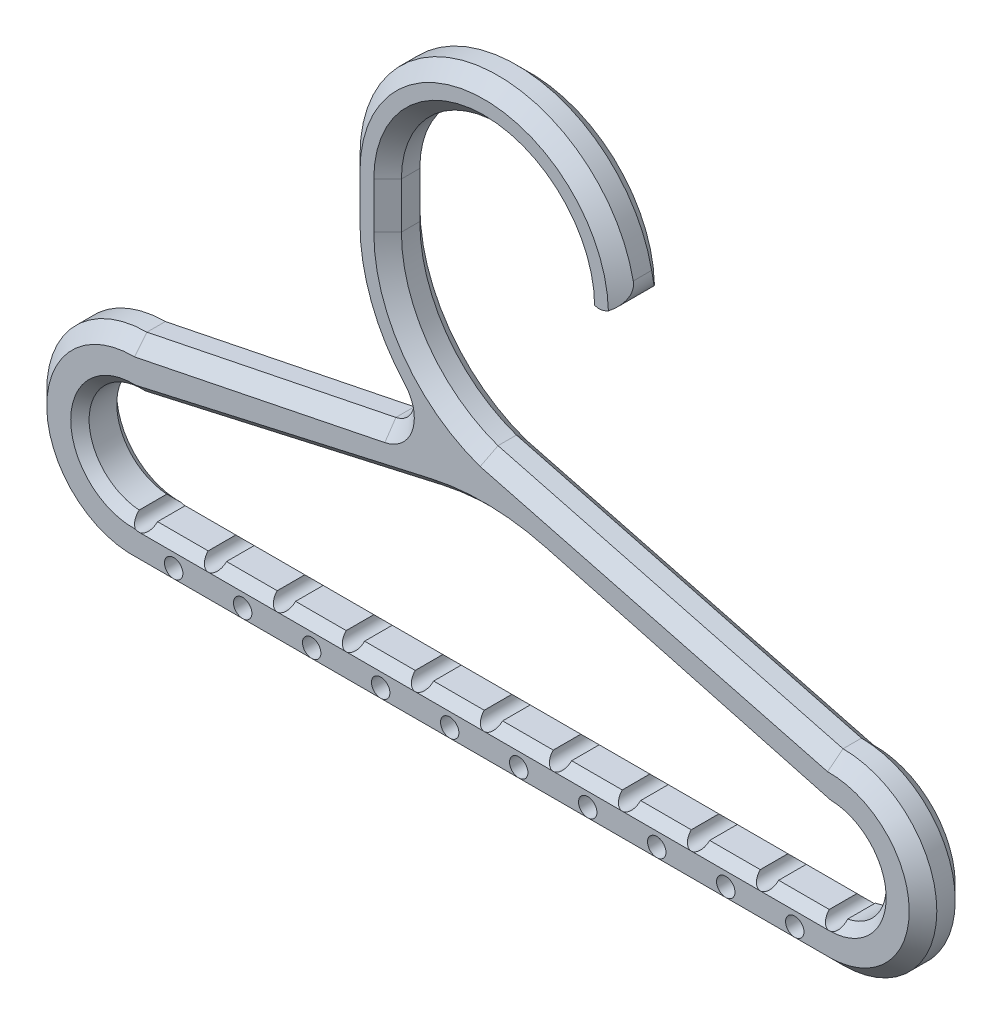
SolidWorks part; units mm, degrees
ref_plane "Front Plane" through (0, 0, 0) normal (0, 0, 1) x (1, 0, 0)
ref_plane "Top Plane" through (0, 0, 0) normal (0, 1, 0) x (1, 0, 0)
ref_plane "Right Plane" through (0, 0, 0) normal (1, 0, 0) x (0, 0, -1)
sketch "Sketch1" plane through (0, 0, 0) normal (0, 0, 1) x (1, 0, 0)
  line L0 (8.5, -40) -> (14, -40)
  line L1 (-36.5, -40) -> (-31, -40)
  line L2 (10.5, 5) -> (15, 5)
  line L3 (-36.5, -40) -> (-31, -40)
  line L5 (-37.5, -45) -> (37.5, -45)
  line L7 (-29, -40) -> (-23.5, -40)
  line L17 (6.4815, -21.2975) -> (37.5, -29.624)
  line L18 (-15, 0) -> (-15, 5)
  line L20 (0, -14.8492) -> (37.5, -24.624)
  line L21 (-11.0987, -17.7384) -> (-38.154, -23.2413)
  line L22 (-5.5107, -21.0576) -> (-37.8126, -28.3574)
  line L23 (-29, -40) -> (-23.5, -40)
  line L24 (-21.5, -40) -> (-16, -40)
  line L25 (-21.5, -40) -> (-16, -40)
  line L26 (-14, -40) -> (-8.5, -40)
  line L27 (-14, -40) -> (-8.5, -40)
  line L28 (-6.5, -40) -> (-1, -40)
  line L29 (-6.5, -40) -> (-1, -40)
  line L30 (1, -40) -> (6.5, -40)
  line L31 (1, -40) -> (6.5, -40)
  line L32 (8.5, -40) -> (14, -40)
  line L33 (16, -40) -> (21.5, -40)
  line L34 (16, -40) -> (21.5, -40)
  line L35 (23.5, -40) -> (29, -40)
  line L36 (23.5, -40) -> (29, -40)
  line L37 (31, -40) -> (36.5, -40)
  line L38 (31, -40) -> (36.5, -40)
  line L39 (-10.5, 0) -> (-10.5, 5)
  line L41 (-15, 5) -> (-15, 0)
  arc A2 (-10.5, 0) -> (0, -14.8492) centre (5.25, 0) ccw
  arc A3 (-15, 0) -> (-9.7457, -13.6085) centre (5.25, 0) ccw
  arc A7 (-9.7457, -13.6085) -> (-11.0987, -17.7384) centre (-11.597, -15.2886) cw
  arc A8 (38.4953, -39.9036) -> (37.5, -29.624) centre (37.5, -34.812) ccw
  arc A9 (37.5, -45) -> (37.5, -24.624) centre (37.5, -34.812) ccw
  arc A10 (-37.5, -45) -> (-38.154, -23.2413) centre (-38.154, -34.1305) cw
  arc A11 (-38.4953, -39.9036) -> (-37.8126, -28.3574) centre (-38.154, -34.1305) cw
  arc A12 (6.4815, -21.2975) -> (-5.5107, -21.0576) centre (0, -45.4427) ccw
  arc A13 (36.5, -40) -> (38.4953, -39.9036) centre (37.5, -40) ccw
  arc A14 (29, -40) -> (31, -40) centre (30, -40) ccw
  arc A15 (21.5, -40) -> (23.5, -40) centre (22.5, -40) ccw
  arc A16 (14, -40) -> (16, -40) centre (15, -40) ccw
  arc A17 (6.5, -40) -> (8.5, -40) centre (7.5, -40) ccw
  arc A18 (-1, -40) -> (1, -40) centre (0, -40) ccw
  arc A19 (-8.5, -40) -> (-6.5, -40) centre (-7.5, -40) ccw
  arc A20 (-16, -40) -> (-14, -40) centre (-15, -40) ccw
  arc A21 (-23.5, -40) -> (-21.5, -40) centre (-22.5, -40) ccw
  arc A22 (-31, -40) -> (-29, -40) centre (-30, -40) ccw
  arc A23 (-38.4953, -39.9036) -> (-36.5, -40) centre (-37.5, -40) ccw
  circle A24 centre (-33.75, -42.5) radius 1
  circle A25 centre (-26.25, -42.5) radius 1
  circle A26 centre (-18.75, -42.5) radius 1
  circle A27 centre (-11.25, -42.5) radius 1
  circle A28 centre (-3.75, -42.5) radius 1
  circle A29 centre (3.75, -42.5) radius 1
  circle A30 centre (11.25, -42.5) radius 1
  circle A31 centre (18.75, -42.5) radius 1
  circle A32 centre (26.25, -42.5) radius 1
  circle A33 centre (33.75, -42.5) radius 1
  arc A36 (15, 5) -> (-15, 5) centre (0, 5) ccw
  arc A37 (10.5, 5) -> (-10.5, 5) centre (0, 5) ccw
  point P9 (0.5, -40)
  dimension "D5" = 2.5
  dimension "D7" = 25
  dimension "D8" = 2
  dimension "D4" = 2
  dimension "D3" = 5
  dimension "D6" = 10
  dimension "D10" = 5
  dimension "D9" = 11
extrude "Boss-Extrude1" add sketch "Sketch1" along normal blind 5 contours A37 L2 A36 L18 A3 A7 L21 A10 L5 A9 L20 A2 L39 A33 A32 A31 A30 A29 A28 A27 A26 A25 A24 A23 A11 L22 A12 L17 A8 A13 L37 A14 L35 A15 L33 A16 L0 A17 L30 A18
ref_plane "Plane1" through (0, 0, 2.5) normal (0, 0, 1) x (1, 0, 0)
chamfer "Chamfer1" distance 1.5 angle 45 12 edges at (-7.6098, -9.0933, 5) (-10.5, 2.5, 5) (0, 15.5, 5) (0, -45, 5) (47.688, -34.812, 5) (18.75, -19.7366, 5) (0, 20, 5) (-15, 2.5, 5) (-13.6408, -7.2938, 5) (-9.2213, -16.0669, 5) (-49.0382, -34.4576, 5) (-24.6263, -20.4899, 5)
chamfer "Chamfer2" distance 1.5 angle 45 12 edges at (-49.0382, -34.4576, 0) (-7.6098, -9.0933, 0) (-10.5, 2.5, 0) (0, 15.5, 0) (0, -45, 0) (47.688, -34.812, 0) (18.75, -19.7366, 0) (-24.6263, -20.4899, 0) (-9.2213, -16.0669, 0) (-13.6408, -7.2938, 0) (-15, 2.5, 0) (0, 20, 0)
chamfer "Chamfer3" distance 1 angle 45 23 edges at (-43.9271, -33.7891, 5) (-33.75, -40, 5) (-26.25, -40, 5) (-18.75, -40, 5) (-11.25, -40, 5) (-3.75, -40, 5) (3.75, -40, 5) (11.25, -40, 5) (18.75, -40, 5) (26.25, -40, 5) (33.75, -40, 5) (42.6638, -34.312, 0) (-43.9271, -33.7891, 0) (-33.75, -40, 0) (-26.25, -40, 0) (-18.75, -40, 0) (-11.25, -40, 0) (-3.75, -40, 0) (3.75, -40, 0) (11.25, -40, 0) (18.75, -40, 0) (26.25, -40, 0) (33.75, -40, 0)
chamfer "Chamfer4" distance 1 7 edges at (-20.5467, -24.4555, 0) (0.5, -20.4477, 0) (20.8868, -25.1644, 0) (21.9907, -25.4608, 5) (0.5, -20.4477, 5) (-20.5467, -24.4555, 5) (42.6638, -34.312, 5)
fillet "Fillet1" radius 2.5 2 edges at (15, 5, 2.5) (10.5, 5, 2.5)
